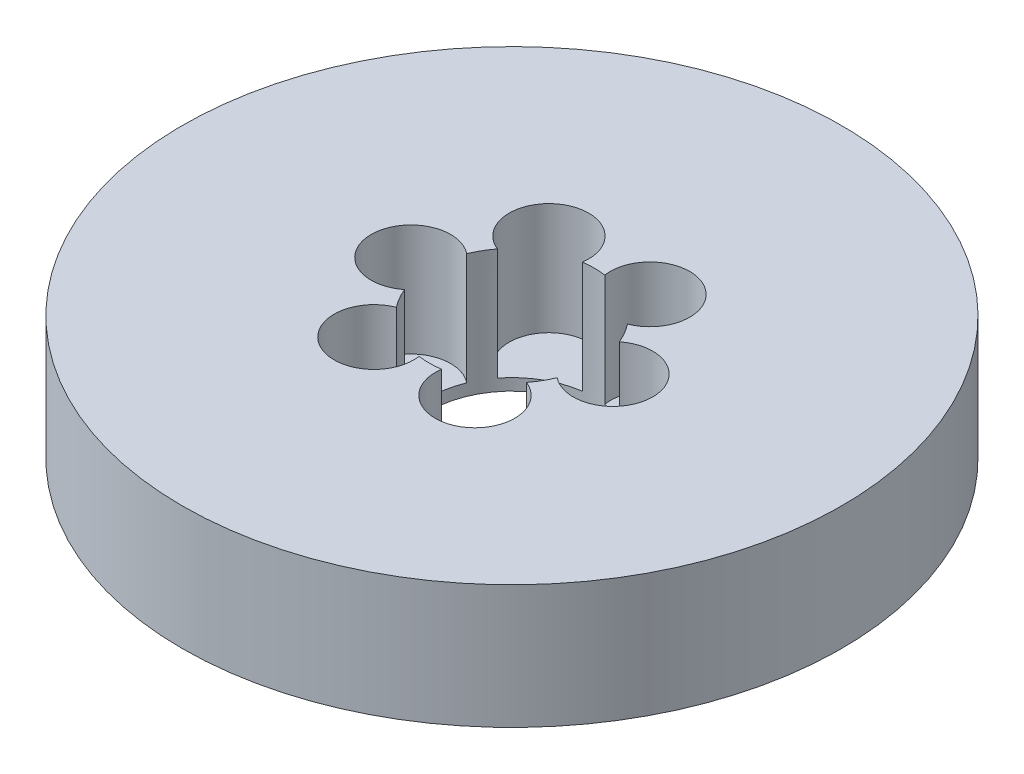
SolidWorks part; units mm, degrees
ref_plane "Front Plane" through (0, 0, 0) normal (0, 0, 1) x (1, 0, 0)
ref_plane "Top Plane" through (0, 0, 0) normal (0, 1, 0) x (1, 0, 0)
ref_plane "Right Plane" through (0, 0, 0) normal (1, 0, 0) x (0, 0, -1)
sketch "Sketch1" plane through (0, 0, 0) normal (0, 1, 0) x (1, 0, 0)
  circle A0 centre (0, 0) radius 80
  dimension "FLANGE_OD" = 160
extrude "Boss-Extrude1" add sketch "Sketch1" along normal blind 30
sketch "Sketch2" plane through (0, 0, 0) normal (0, 1, 0) x (1, 0, 0)
  circle A0 centre (0, 0) radius 20
  dimension "BORE_D" = 40
extrude "Cut-Extrude1" cut sketch "Sketch2" along normal through all
sketch "Sketch3" plane through (0, 30, 0) normal (0, 1, 0) x (1, 0, 0)
  circle A0 centre (0, 0) radius 24.5257 construction
  circle A1 centre (-24.5257, 0) radius 9.6463
  dimension "BOLT_D" = 19.2927
  dimension "BOLT_PCD" = 49.0513
extrude "Cut-Extrude2" cut sketch "Sketch3" against normal blind 27.1447
pattern_circular "CirPattern1" count 6 over 360 about axis through (0, 0, 0) along (0, 1, 0) of "Cut-Extrude2"
